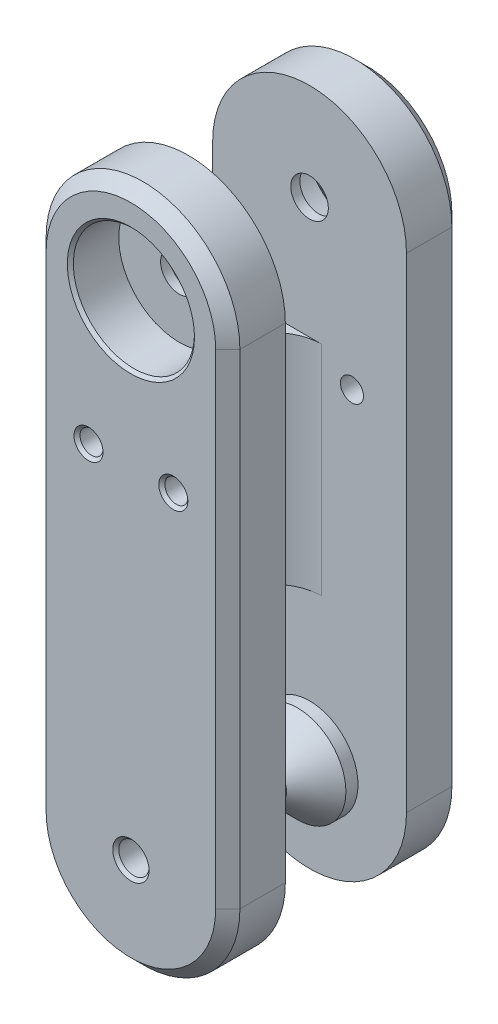
SolidWorks part; units mm, degrees
ref_plane "Front Plane" through (0, 0, 0) normal (0, 0, 1) x (1, 0, 0)
ref_plane "Top Plane" through (0, 0, 0) normal (0, 1, 0) x (1, 0, 0)
ref_plane "Right Plane" through (0, 0, 0) normal (1, 0, 0) x (0, 0, -1)
sketch "Sketch1" plane through (0, 0, 0) normal (0, 0, 1) x (1, 0, 0)
  line L0 (0, 0) -> (0, 40) construction
  line L1 (-8, 0) -> (-8, 40)
  line L2 (8, 0) -> (8, 40)
  arc A0 (-8, 0) -> (8, 0) centre (0, 0) ccw
  arc A1 (8, 40) -> (-8, 40) centre (0, 40) ccw
  circle A2 centre (0, 40) radius 1.55
  circle A3 centre (0, 0) radius 1.25
  point P3 (0, 20)
  dimension "D1" = 3.1
  dimension "D2" = 8
  dimension "D3" = 40
  dimension "D4" = 2.5
extrude "Boss-Extrude1" add sketch "Sketch1" along normal blind 4.75
fillet "Fillet2" radius 1 4 edges at (-8, 20, 4.75) (0, 48, 4.75) (8, 20, 4.75) (0, -8, 4.75) profile chamfer
sketch "Sketch2" plane through (0, 0, 4.75) normal (0, 0, 1) x (1, 0, 0)
  circle A0 centre (0, 40) radius 5
  dimension "D1" = 10
extrude "Cut-Extrude1" cut sketch "Sketch2" against normal blind 4
sketch "Sketch3" plane through (0, 0, 0) normal (0, 0, -1) x (-1, 0, 0)
  line L0 (8, 40) -> (8, 0) construction
  line L1 (8, 30) -> (3, 30)
  line L2 (8, 30) -> (8, 12)
  line L3 (8, 12) -> (3, 12)
  line L4 (3, 30) -> (3, 12) construction
  line L5 (3, 30) -> (3, 12)
  circle A0 centre (0, 40) radius 1.55 construction
  circle A1 centre (0, 0) radius 1.25 construction
  dimension "D1" = 5
  dimension "D2" = 10
  dimension "D3" = 12
extrude "Boss-Extrude2" add sketch "Sketch3" along normal blind 5
sketch "Sketch8" plane through (0, 0, 0) normal (0, 0, -1) x (-1, 0, 0)
  circle A0 centre (0, 0) radius 4
  circle A1 centre (0, 0) radius 1.55
  dimension "D1" = 8
extrude "Boss-Extrude4" add sketch "Sketch8" along normal blind 4
fillet "Fillet3" radius 4 1 edges at (-3, 21, 0)
mirror "Mirror5" about plane through (0, 0, -5) normal (0, 0, 1) of bodies 112 103
sketch "Sketch7" plane through (0, 0, -14.75) normal (0, 0, -1) x (-1, 0, 0)
  line L0 (0, 40) -> (0, 18.9568) construction
  circle A0 centre (-3.5, 28) radius 0.95
  circle A2 centre (3.5, 28) radius 0.95
  dimension "D1" = 1.9
  dimension "D2" = 7
  dimension "D3" = 12
extrude "Cut-Extrude3" cut sketch "Sketch7" against normal through all
ref_plane "Plane1" through (0, 0, -5) normal (0, 0, -1) x (-1, 0, 0)
chamfer "Chaflán1" distance 0.25 angle 45 8 edges at (5, 40, 4.75) (5, 40, -14.75) (1.25, 0, 4.75) (1.25, 0, -14.75) (-2.55, 28, -14.75) (2.55, 28, -14.75) (2.55, 28, 4.75) (-2.55, 28, 4.75)
chamfer "Chaflán2" distance 3 angle 45 2 edges at (-4, 0, -6) (-4, 0, -4)
